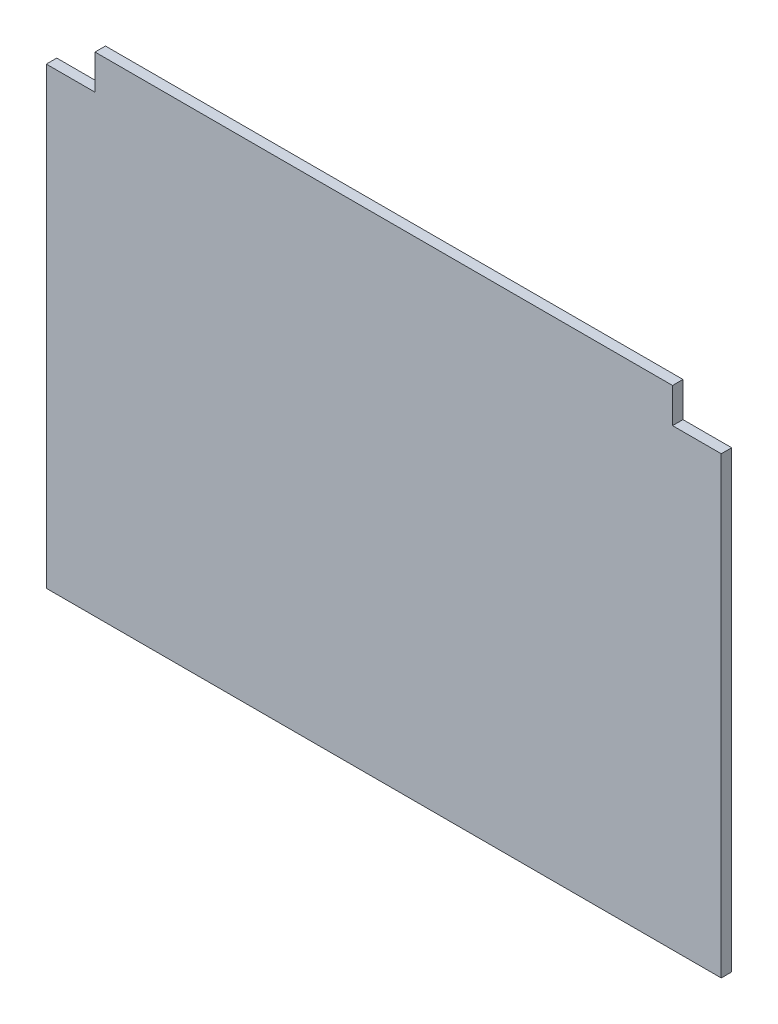
SolidWorks part; units mm, degrees
material "PET"
ref_plane "Front Plane" through (0, 0, 0) normal (0, 0, 1) x (1, 0, 0)
ref_plane "Top Plane" through (0, 0, 0) normal (0, 1, 0) x (1, 0, 0)
ref_plane "Right Plane" through (0, 0, 0) normal (1, 0, 0) x (0, 0, -1)
sketch "Sketch1" plane through (0, 0, 0) normal (0, 0, 1) x (1, 0, 0)
  line L1 (-28.5714, 258.1048) -> (359.4286, 258.1048)
  line L2 (-28.5714, 258.1048) -> (-28.5714, -22.8952)
  line L3 (-28.5714, -22.8952) -> (359.4286, -22.8952)
  line L4 (359.4286, 258.1048) -> (359.4286, -22.8952)
  dimension "D1" = 281
  dimension "D2" = 388
extrude "Boss-Extrude1" add sketch "Sketch1" along normal blind 6
sketch "Sketch2" plane through (0, 0, 6) normal (0, 0, 1) x (1, 0, 0)
  line L1 (-28.5714, 258.1048) -> (-0.5714, 258.1048)
  line L2 (-28.5714, 258.1048) -> (-28.5714, 238.1048)
  line L3 (-28.5714, 238.1048) -> (-0.5714, 238.1048)
  line L4 (-0.5714, 258.1048) -> (-0.5714, 238.1048)
  line L5 (359.4286, 258.1048) -> (331.4286, 258.1048)
  line L6 (359.4286, 258.1048) -> (359.4286, 238.1048)
  line L7 (359.4286, 238.1048) -> (331.4286, 238.1048)
  line L8 (331.4286, 258.1048) -> (331.4286, 238.1048)
  dimension "D1" = 20
  dimension "D2" = 20
  dimension "D3" = 28
  dimension "D4" = 28
extrude "Cut-Extrude1" cut sketch "Sketch2" against normal blind 10
